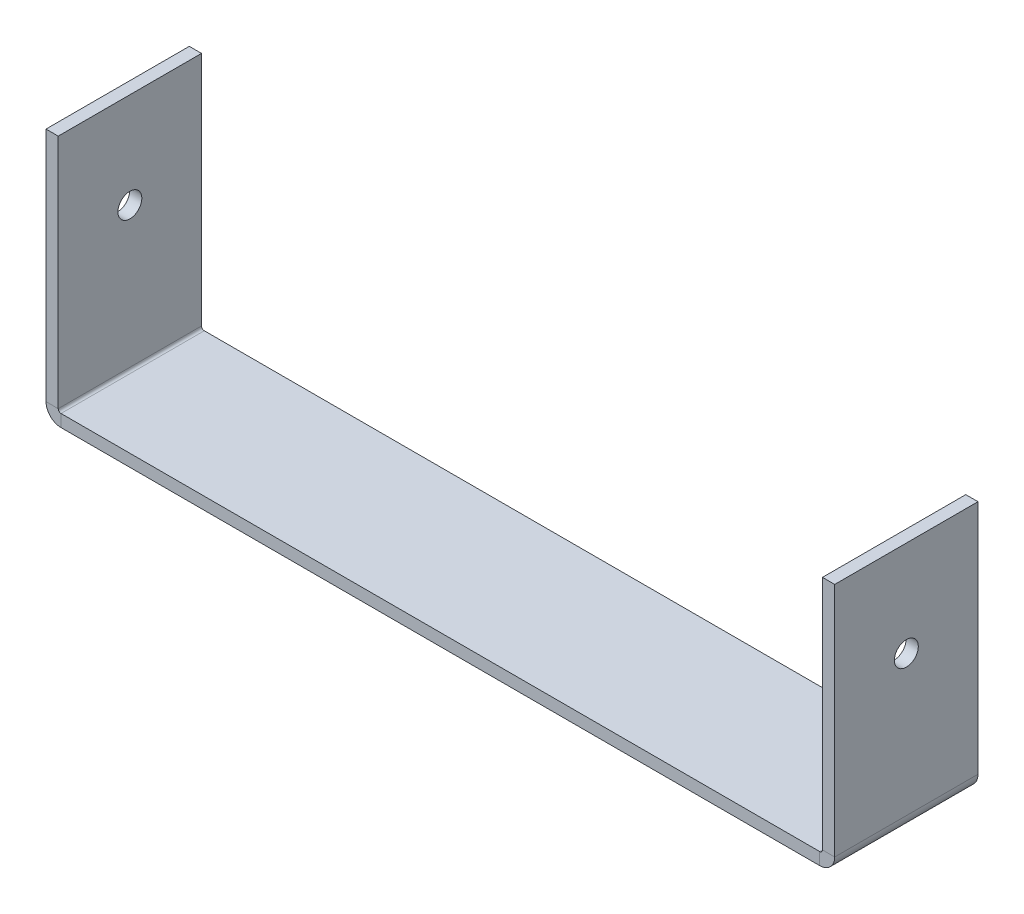
SolidWorks part; units mm, degrees
note: The reader was unsure of these and kept them because the rebuilt part matched: flange length of "Edge-Flange1".
material "Plain Carbon Steel"
ref_plane "Front" through (0, 0, 0) normal (0, 0, 1) x (1, 0, 0)
ref_plane "Top" through (0, 0, 0) normal (0, 1, 0) x (1, 0, 0)
ref_plane "Right" through (0, 0, 0) normal (1, 0, 0) x (0, 0, -1)
sketch "Sketch1" plane through (0, 0, 0) normal (0, 1, 0) x (1, 0, 0)
  line L1 (-101.6, 19.05) -> (101.6, 19.05)
  line L2 (-101.6, 19.05) -> (-101.6, -19.05)
  line L3 (-101.6, -19.05) -> (101.6, -19.05)
  line L4 (101.6, 19.05) -> (101.6, -19.05)
  point P4 (0, 19.05)
  point P5 (-101.6, 0)
  dimension "D1" = 203.2
  dimension "D2" = 38.1
sheet metal parameters "Sheet-Metal1" thickness 3.2512 parameters "D1"=0.7366
base flange "Base-Flange1" sketch "Sketch1" thickness 3.2512 reverse thickness direction no parameters "D1"=0.7366
edge flange "Edge-Flange1" sketch "Sketch8" flange profiles "Sketch8", "Sketch9" flange angle 90 flange length 66.7512 flange position material outside bend radius 0.7366 thickness 3.2512 relief rectangular parameters "D6"=10, "D8"=0.254
sketch "Sketch8" plane through (-101.6, 0, 0) normal (-1, 0, 0) x (0, 0, 1)
  line L0 (-19.05, 0) -> (19.05, 0) construction
  line L1 (-19.05, 0) -> (19.05, 0)
  line L2 (-19.05, 0) -> (-19.05, 63.5)
  line L3 (-19.05, 63.5) -> (19.05, 63.5)
  line L4 (19.05, 63.5) -> (19.05, 0)
  dimension "D1" = 63.5
sketch "Sketch9" plane through (101.6, 0, 0) normal (1, 0, 0) x (0, 0, -1)
  line L0 (-19.05, 0) -> (19.05, 0) construction
  line L1 (-19.05, 0) -> (19.05, 0)
  line L2 (-19.05, 0) -> (-19.05, 63.5)
  line L3 (-19.05, 63.5) -> (19.05, 63.5)
  line L4 (19.05, 63.5) -> (19.05, 0)
bend "EdgeBend1" bend radius 0.7366 bend angle 90 parameters "D5"=1
bend "EdgeBend2" bend radius 0.7366 bend angle 90 parameters "D5"=2
sketch "Sketch10" plane through (-104.8512, 0, 0) normal (-1, 0, 0) x (0, 0, 1)
  line L0 (19.05, 63.5) -> (-19.05, 63.5) construction
  circle A0 centre (0, 38.1) radius 3.175
  point P4 (0, 63.5)
  dimension "D1" = 6.35
  dimension "D2" = 25.4
extrude "Cut-Extrude1" cut sketch "Sketch10" against normal through all normal cut yes
flat pattern "Flat-Pattern1" [suppressed]
sketch "Bend-Lines1" plane through (0, 0, 0) normal (0, 1, 0) x (-1, 0, 0)
sketch3d "Bounding-Box1" [suppressed]
  line L0 (203.2, 0, 0) -> (0, 0, 0) construction
  line L1 (203.2, -38.1, 0) -> (0, -38.1, 0) construction
  line L2 (203.2, 0, 0) -> (203.2, -38.1, 0) construction
  line L3 (0, 0, 0) -> (0, -38.1, 0) construction
bend of the flat pattern "Flatten-<EdgeBend1>1"
bend of the flat pattern "Flatten-<EdgeBend2>1"
